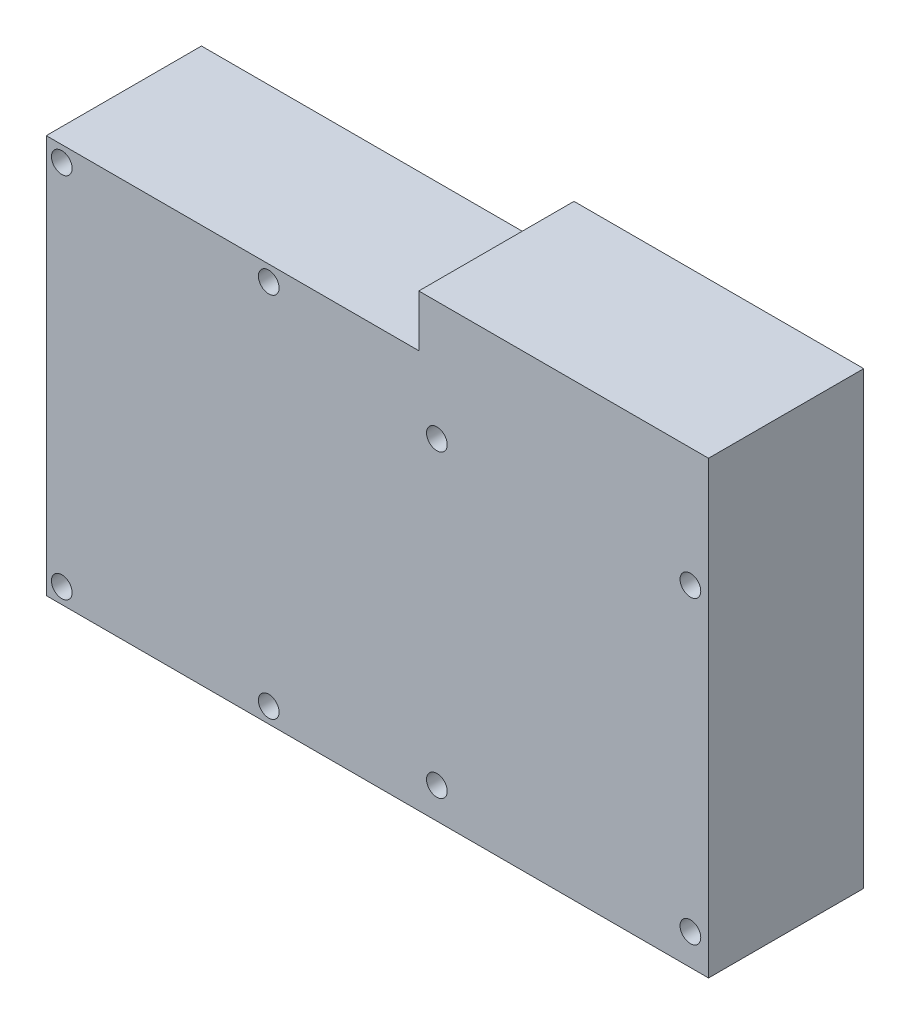
SolidWorks part; units mm, degrees
ref_plane "Plan de face" through (0, 0, 0) normal (0, 0, 1) x (1, 0, 0)
ref_plane "Plan de dessus" through (0, 0, 0) normal (0, 1, 0) x (1, 0, 0)
ref_plane "Plan de droite" through (0, 0, 0) normal (1, 0, 0) x (0, 0, -1)
sketch "Esquisse1" plane through (0, 0, 0) normal (0, 0, 1) x (1, 0, 0)
  line L0 (0, 0) -> (128, 0)
  line L1 (128, 0) -> (128, 87)
  line L2 (128, 87) -> (72, 87)
  line L3 (72, 87) -> (72, 77)
  line L4 (72, 77) -> (0, 77)
  line L5 (0, 77) -> (0, 0)
  line L7 (3, 74) -> (43, 74) construction
  line L8 (3, 74) -> (3, 3) construction
  line L9 (3, 3) -> (43, 3) construction
  line L10 (43, 74) -> (43, 3) construction
  line L11 (75.5, 64) -> (124.5, 64) construction
  line L12 (75.5, 64) -> (75.5, 6) construction
  line L13 (75.5, 6) -> (124.5, 6) construction
  line L14 (124.5, 64) -> (124.5, 6) construction
  circle A0 centre (3, 74) radius 2
  circle A1 centre (43, 74) radius 2
  circle A2 centre (3, 3) radius 2
  circle A3 centre (43, 3) radius 2
  circle A4 centre (75.5, 64) radius 2
  circle A5 centre (124.5, 64) radius 2
  circle A6 centre (75.5, 6) radius 2
  circle A7 centre (124.5, 6) radius 2
  dimension "D1" = 128
  dimension "D2" = 87
  dimension "D3" = 77
  dimension "D4" = 56
  dimension "D5" = 43
  dimension "D6" = 3
  dimension "D7" = 3
  dimension "D8" = 3
  dimension "D9" = 6
  dimension "D10" = 3.5
  dimension "D11" = 49
  dimension "D12" = 58
extrude "Boss.-Extru.1" add sketch "Esquisse1" against normal blind 30
sketch "Esquisse2" plane through (0, 0, 0) normal (0, 0, 1) x (1, 0, 0)
  text T0 "<b>Raspberry Pi 4</b>"
  text T1 "<b>DE0 Nano</b>\r\n\r\n"
